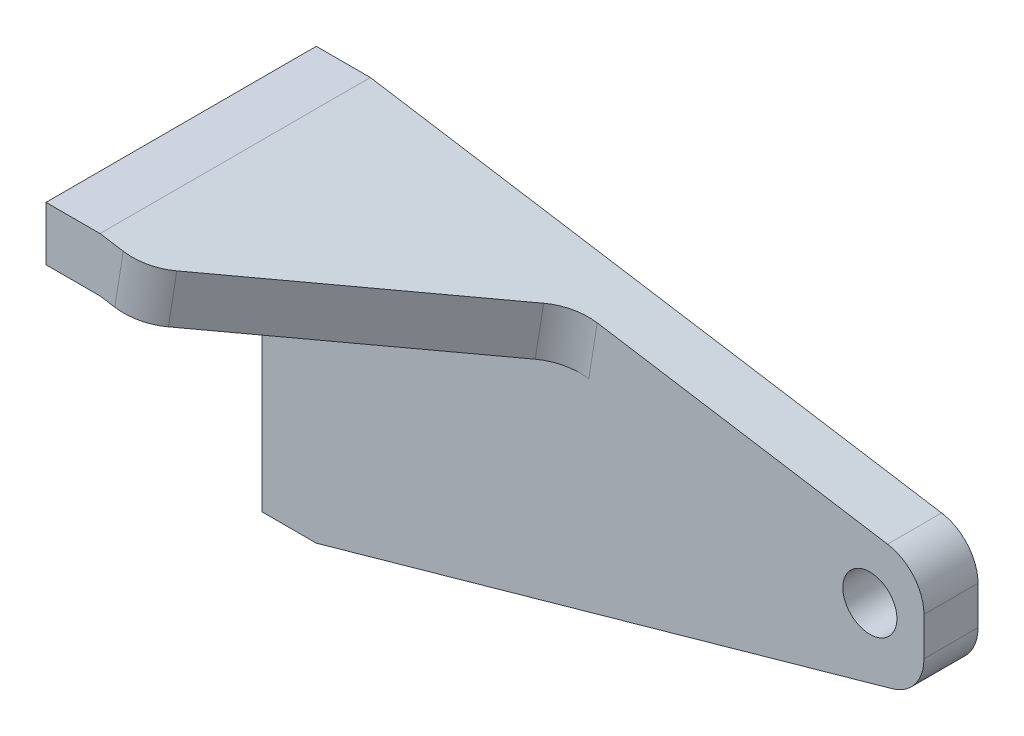
SolidWorks part; units mm, degrees
ref_plane "Front Plane" through (0, 0, 0) normal (0, 0, 1) x (1, 0, 0)
ref_plane "Top Plane" through (0, 0, 0) normal (0, 1, 0) x (1, 0, 0)
ref_plane "Right Plane" through (0, 0, 0) normal (1, 0, 0) x (0, 0, -1)
sketch "Sketch1" plane through (0, 0, -69.2512) normal (0, 0, 1) x (1, 0, 0)
  line L1 (-122.6968, 61.2355) -> (-119.5218, 61.2355) construction
  line L2 (-122.6968, 83.3335) -> (-119.5218, 83.3335)
  line L3 (-122.6968, 83.3335) -> (-122.6968, 61.2355)
  line L4 (-122.6968, 61.2355) -> (-119.5218, 61.2355)
  line L5 (-119.5218, 61.2355) -> (-85.6874, 70.7476)
  line L6 (-83.8348, 73.1928) -> (-83.8348, 75.4529)
  line L7 (-85.9732, 77.9609) -> (-119.5218, 83.3335)
  line L8 (-119.5218, 83.3335) -> (-85.9732, 77.9609)
  line L9 (-87.0098, 74.4435) -> (-81.9897, 74.4435) construction
  arc A1 (-83.8348, 75.4529) -> (-85.9732, 77.9609) centre (-86.3748, 75.4529) ccw
  arc A2 (-85.6874, 70.7476) -> (-83.8348, 73.1928) centre (-86.3748, 73.1928) ccw
  circle A3 centre (-87.0098, 74.4435) radius 1.5875
  point P15 (-83.8348, 77.6185)
  point P18 (-83.8348, 71.2685)
  dimension "D3" = 2.54
  dimension "D4" = 3.175
  dimension "D1" = 6.35
  dimension "D2" = 3.175
extrude "Boss-Extrude1" add sketch "Sketch1" along normal blind 3.175
sketch "Sketch2" plane through (0, 0, -66.0762) normal (0, 0, 1) x (1, 0, 0)
  line L7 (-85.9732, 77.9609) -> (-119.5218, 83.3335) construction
  line L8 (-85.9732, 77.9609) -> (-119.5218, 83.3335)
  line L9 (-85.9732, 77.9609) -> (-119.5218, 83.3335)
  line L10 (-122.6968, 83.3335) -> (-122.6968, 61.2355)
  line L11 (-122.6968, 61.2355) -> (-119.5218, 61.2355)
  line L12 (-125.8718, 83.3335) -> (-122.6968, 83.3335)
  line L13 (-125.8718, 83.3335) -> (-125.8718, 80.1585)
  line L14 (-125.8718, 80.1585) -> (-122.6968, 80.1585)
  line L15 (-122.6968, 83.3335) -> (-122.6968, 80.1585)
  line L16 (-103.3179, 80.7385) -> (-103.8136, 77.6429)
  line L17 (-119.5218, 61.2355) -> (-85.6874, 70.7476)
  line L18 (-103.8136, 77.6429) -> (-119.5218, 80.1585)
  line L22 (-122.6968, 83.3335) -> (-122.6968, 61.2355) construction
  line L23 (-83.8348, 73.1928) -> (-83.8348, 75.4529)
  line L24 (-83.8348, 73.1928) -> (-83.8348, 75.4529)
  line L25 (-119.5218, 83.3335) -> (-122.6968, 83.3335)
  line L26 (-122.6968, 80.1585) -> (-119.5218, 80.1585) construction
  line L27 (-119.5218, 80.1585) -> (-122.6968, 80.1585)
  line L28 (-119.5218, 83.3335) -> (-122.6968, 83.3335)
  line L29 (-122.6968, 83.3335) -> (-122.6968, 80.1585)
  arc A2 (-85.6874, 70.7476) -> (-83.8348, 73.1928) centre (-86.3748, 73.1928) ccw
  arc A3 (-85.6874, 70.7476) -> (-83.8348, 73.1928) centre (-86.3748, 73.1928) ccw
  arc A4 (-83.8348, 75.4529) -> (-85.9732, 77.9609) centre (-86.3748, 75.4529) ccw
  arc A5 (-83.8348, 75.4529) -> (-85.9732, 77.9609) centre (-86.3748, 75.4529) ccw
  dimension "D2" = 19.05
  dimension "D1" = 0
extrude "Boss-Extrude2" add sketch "Sketch2" along normal up to surface (12.7 mm away)
chamfer "Chamfer1" distance 13.716 angle 45 1 edges at (-103.5658, 79.1907, -53.3762)
fillet "Fillet1" radius 3.175 2 edges at (-117.1092, 81.3596, -53.3762) (-104.569, 79.3514, -66.0762)
